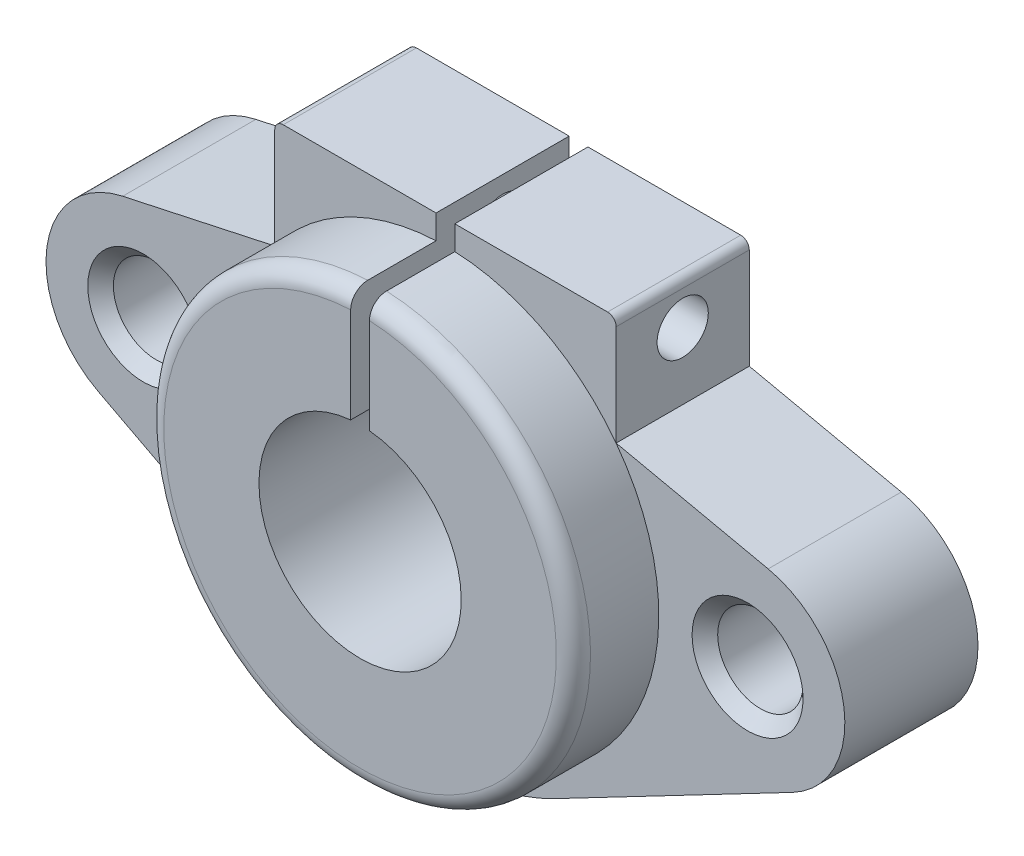
SolidWorks part; units mm, degrees
ref_plane "Alzado" through (0, 0, 0) normal (0, 0, 1) x (1, 0, 0)
ref_plane "Planta" through (0, 0, 0) normal (0, 1, 0) x (1, 0, 0)
ref_plane "Vista lateral" through (0, 0, 0) normal (1, 0, 0) x (0, 0, -1)
sketch "Croquis1" plane through (0, 0, 0) normal (0, 0, 1) x (1, 0, 0)
  circle A0 centre (0, 0) radius 12.5
  circle A1 centre (0, 0) radius 5.925
  dimension "D1" = 25
  dimension "D2" = 11.85
extrude "Saliente-Extruir1" add sketch "Croquis1" along normal blind 12.8
sketch "Croquis2" plane through (0, 0, 0) normal (0, 0, -1) x (-1, 0, 0)
  line L0 (-17.7, 0) -> (17.7, 0) construction
  line L1 (-6.4395, -12.3184) -> (-20.3407, -5.0514)
  line L2 (6.4395, -12.3184) -> (20.3407, -5.0514)
  line L3 (0, 0) -> (0, 13.9) construction
  line L4 (-10, 13.9) -> (10, 13.9)
  line L5 (-10, 13.9) -> (-10, 7.5)
  line L6 (10, 13.9) -> (10, 7.5)
  line L7 (-10, 7.5) -> (-18.9066, 5.5708)
  line L8 (10, 7.5) -> (18.9066, 5.5708)
  circle A0 centre (0, 0) radius 13.9 construction
  circle A1 centre (-17.7, 0) radius 5.7 construction
  circle A2 centre (17.7, 0) radius 5.7 construction
  arc A3 (-6.4395, -12.3184) -> (6.4395, -12.3184) centre (0, 0) ccw
  circle A4 centre (0, 0) radius 12.5 construction
  arc A5 (-20.3407, -5.0514) -> (-18.9066, 5.5708) centre (-17.7, 0) cw
  arc A6 (18.9066, 5.5708) -> (20.3407, -5.0514) centre (17.7, 0) cw
  circle A7 centre (0, 0) radius 12.5 construction
  circle A8 centre (0, 0) radius 5.925 construction
  circle A9 centre (0, 0) radius 5.925
  point P4 (0, 0)
  point P19 (0, 13.9)
  dimension "D2" = 27.8
  dimension "D3" = 11.4
  dimension "D4" = 11.4
  dimension "D1" = 35.4
  dimension "D5" = 20
extrude "Saliente-Extruir2" add sketch "Croquis2" against normal blind 7.8
sketch "Croquis3" plane through (0, 0, 0) normal (0, 0, -1) x (-1, 0, 0)
  circle A0 centre (-17.7, 0) radius 2.5
  circle A1 centre (17.7, 0) radius 2.5
  point P0 (-17.7, 0)
  point P1 (17.7, 0)
  dimension "D1" = 5
extrude "Cortar-Extruir1" cut sketch "Croquis3" against normal up to vertex (7.8 mm away) up to point (-10, 7.5, 7.8)
sketch "Croquis4" plane through (0, 0, 0) normal (0, 0, -1) x (-1, 0, 0)
  line L0 (0, 0) -> (0, 13.9) construction
  line L1 (10, 13.9) -> (-10, 13.9) construction
  line L2 (-0.55, 13.9) -> (0.55, 13.9)
  line L3 (0.55, 13.9) -> (0.55, 5.8994)
  line L4 (-0.55, 13.9) -> (-0.55, 5.8994)
  circle A0 centre (0, 0) radius 5.925 construction
  circle A1 centre (0, 0) radius 5.925 construction
  arc A2 (-0.55, 5.8994) -> (0.5766, 5.8969) centre (0, 0) cw
  point P10 (0, 13.9)
  line M7 (10, 13.9) -> (-10, 13.9)
  circle M15 centre (0, 0) radius 5.925
  dimension "D1" = 1.1
extrude "Cortar-Extruir2" cut sketch "Croquis4" against normal blind 13 contours L4 L3 M7 M15 region at (0, 9.9082, 0)
fillet "Redondeo1" radius 1 1 edges at (0, -12.5, 12.8)
sketch "Croquis5" plane through (10, 0, 0) normal (1, 0, 0) x (0, 0, -1)
  line L0 (-7.8, 11.4) -> (0, 11.4) construction
  line L1 (-7.8, 13.9) -> (-7.8, 7.5) construction
  line L2 (0, 13.9) -> (0, 7.5) construction
  line L3 (-7.8, 13.9) -> (0, 13.9) construction
  circle A0 centre (-3.9, 11.4) radius 1.5
  dimension "D1" = 3
  dimension "D2" = 2.5
extrude "Cortar-Extruir3" cut sketch "Croquis5" against normal up to vertex (20 mm away) up to point (-10, 13.9, 7.8)
fillet "Redondeo2" radius 0.5 2 edges at (-10, 13.9, 3.9) (10, 13.9, 3.9)
chamfer "Chaflán1" distance 0.75 angle 45 2 edges at (-20.2, 0, 7.8) (15.2, 0, 7.8)
equation "\"D4@Croquis2\"=\"D3@Croquis2\""
